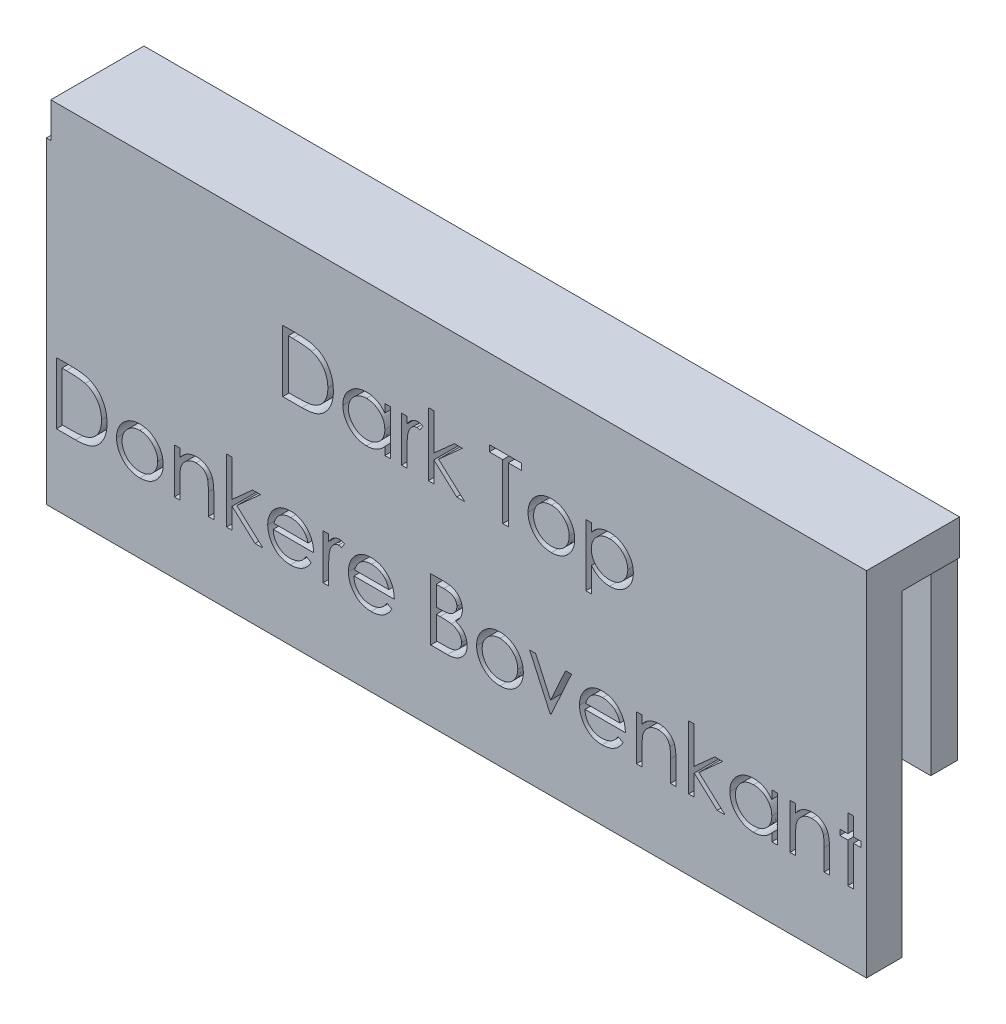
SolidWorks part; units mm, degrees
ref_plane "Front Plane" through (0, 0, 0) normal (0, 0, 1) x (1, 0, 0)
ref_plane "Top Plane" through (0, 0, 0) normal (0, 1, 0) x (1, 0, 0)
ref_plane "Right Plane" through (0, 0, 0) normal (1, 0, 0) x (0, 0, -1)
sketch "Sketch1" plane through (0, 0, 0) normal (0, 0, 1) x (1, 0, 0)
  line L0 (61.5, 25) -> (3, 25) construction
  line L1 (9, 25) -> (55.5, 25)
  line L2 (9, 25) -> (9, 7)
  line L3 (9, 7) -> (55.5, 7)
  line L4 (55.5, 25) -> (55.5, 7)
  line L5 (55.5, 15) -> (55.5, 25) construction
  line L6 (9, 15) -> (9, 25) construction
  line L7 (2, 2) -> (62.5, 2) construction
  dimension "D1" = 5
extrude "Boss-Extrude1" add sketch "Sketch1" along normal blind 2
sketch "Sketch3" plane through (0, 15, 0) normal (0, 1, 0) x (1, 0, 0)
  line L0 (9.2511, 3.2803) -> (9.2511, 1.7537)
  line L5 (9.2511, 1.7537) -> (55.39, 1.7537)
  line L6 (55.39, 3.2803) -> (55.39, 1.7537)
  line L7 (9.2511, 3.2803) -> (55.39, 3.2803)
extrude "Boss-Extrude2" add sketch "Sketch3" along normal up to surface (10 mm away) separate body
sketch "Sketch4" plane through (0, 25, 0) normal (0, 1, 0) x (1, 0, 0)
  line L1 (9.2511, 3.2803) -> (55.5, 3.2803)
  line L2 (9.2511, 3.2803) -> (9.2511, -2)
  line L3 (9.2511, -2) -> (55.5, -2)
  line L4 (55.5, 3.2803) -> (55.5, -2)
extrude "Boss-Extrude3" add sketch "Sketch4" along normal blind 2
sketch "Sketch5" plane through (0, 0, 2) normal (0, 0, 1) x (1, 0, 0)
  line L0 (9, 19) -> (55.5, 19) construction
  line L1 (9, 25) -> (9, 7) construction
  line L2 (55.5, 7) -> (55.5, 27) construction
  line L3 (9.2511, 27) -> (55.5, 27) construction
  line L4 (9, 11) -> (55.5, 11) construction
  line L161 (22.4006, 19) -> (22.4006, 22.5)
  line L162 (22.4006, 22.5) -> (23.1074, 22.5)
  line L163 (23.4853, 19) -> (22.4006, 19)
  line L164 (22.7147, 19.359) -> (23.1165, 19.359)
  line L165 (22.9608, 22.141) -> (22.7147, 22.141)
  line L166 (22.7147, 22.141) -> (22.7147, 19.359)
  line L167 (28.5032, 21.5577) -> (28.5032, 19)
  line L168 (28.5032, 19) -> (28.1891, 19)
  line L169 (28.1891, 19) -> (28.1891, 19.4424)
  line L170 (28.1891, 21.0844) -> (28.1891, 21.5577)
  line L171 (28.1891, 21.5577) -> (28.5032, 21.5577)
  line L172 (29.1314, 21.5577) -> (29.4455, 21.5577)
  line L173 (29.4455, 21.5577) -> (29.4455, 21.1812)
  line L174 (30.3429, 21.5149) -> (30.1705, 21.2429)
  line L175 (29.4455, 19.8596) -> (29.4455, 19)
  line L176 (29.4455, 19) -> (29.1314, 19)
  line L177 (29.1314, 19) -> (29.1314, 21.5577)
  line L178 (30.6571, 22.5897) -> (30.9712, 22.5897)
  line L179 (30.9712, 22.5897) -> (30.9712, 20.5144)
  line L180 (30.9712, 20.5144) -> (32.135, 21.5577)
  line L181 (32.135, 21.5577) -> (32.5865, 21.5577)
  line L182 (32.5865, 21.5577) -> (31.2362, 20.3462)
  line L183 (31.2362, 20.3462) -> (32.7212, 19)
  line L184 (32.7212, 19) -> (32.2703, 19)
  line L185 (32.2703, 19) -> (30.9712, 20.1786)
  line L186 (30.9712, 20.1786) -> (30.9712, 19)
  line L187 (30.9712, 19) -> (30.6571, 19)
  line L188 (30.6571, 19) -> (30.6571, 22.5897)
  line L189 (34.1122, 22.141) -> (34.1122, 22.5)
  line L190 (34.1122, 22.5) -> (35.9519, 22.5)
  line L191 (35.9519, 22.5) -> (35.9519, 22.141)
  line L192 (35.9519, 22.141) -> (35.1891, 22.141)
  line L193 (35.1891, 22.141) -> (35.1891, 19)
  line L194 (35.1891, 19) -> (34.875, 19)
  line L195 (34.875, 19) -> (34.875, 22.141)
  line L196 (34.875, 22.141) -> (34.1122, 22.141)
  line L197 (39.5865, 21.5577) -> (39.9006, 21.5577)
  line L198 (39.9006, 21.5577) -> (39.9006, 21.0844)
  line L199 (39.9006, 19.4634) -> (39.9006, 18.0577)
  line L200 (39.9006, 18.0577) -> (39.5865, 18.0577)
  line L201 (39.5865, 18.0577) -> (39.5865, 21.5577)
  line L202 (9.5673, 11) -> (9.5673, 14.5)
  line L203 (9.5673, 14.5) -> (10.274, 14.5)
  line L204 (10.6519, 11) -> (9.5673, 11)
  line L205 (9.8814, 11.359) -> (10.2832, 11.359)
  line L206 (10.1275, 14.141) -> (9.8814, 14.141)
  line L207 (9.8814, 14.141) -> (9.8814, 11.359)
  line L208 (16.2532, 13.5577) -> (16.5673, 13.5577)
  line L209 (16.5673, 13.5577) -> (16.5673, 13.0964)
  line L210 (18.4968, 12.3062) -> (18.4968, 11)
  line L211 (18.4968, 11) -> (18.1827, 11)
  line L212 (18.1827, 11) -> (18.1827, 12.2031)
  line L213 (16.5673, 11.9248) -> (16.5673, 11)
  line L214 (16.5673, 11) -> (16.2532, 11)
  line L215 (16.2532, 11) -> (16.2532, 13.5577)
  line L216 (19.2147, 14.5897) -> (19.5288, 14.5897)
  line L217 (19.5288, 14.5897) -> (19.5288, 12.5144)
  line L218 (19.5288, 12.5144) -> (20.6927, 13.5577)
  line L219 (20.6927, 13.5577) -> (21.1442, 13.5577)
  line L220 (21.1442, 13.5577) -> (19.7939, 12.3462)
  line L221 (19.7939, 12.3462) -> (21.2788, 11)
  line L222 (21.2788, 11) -> (20.828, 11)
  line L223 (20.828, 11) -> (19.5288, 12.1786)
  line L224 (19.5288, 12.1786) -> (19.5288, 11)
  line L225 (19.5288, 11) -> (19.2147, 11)
  line L226 (19.2147, 11) -> (19.2147, 14.5897)
  line L227 (23.737, 11.8077) -> (24.016, 11.6612)
  line L228 (24.1506, 12.2115) -> (21.8622, 12.2115)
  line L229 (21.8951, 12.5256) -> (23.8365, 12.5256)
  line L230 (24.6891, 13.5577) -> (25.0032, 13.5577)
  line L231 (25.0032, 13.5577) -> (25.0032, 13.1812)
  line L232 (25.9006, 13.5149) -> (25.7282, 13.2429)
  line L233 (25.0032, 11.8596) -> (25.0032, 11)
  line L234 (25.0032, 11) -> (24.6891, 11)
  line L235 (24.6891, 11) -> (24.6891, 13.5577)
  line L236 (28.3139, 11.8077) -> (28.5929, 11.6612)
  line L237 (28.7276, 12.2115) -> (26.4391, 12.2115)
  line L238 (26.4721, 12.5256) -> (28.4135, 12.5256)
  line L239 (30.7917, 14.5) -> (31.4746, 14.5)
  line L240 (31.7382, 11) -> (30.7917, 11)
  line L241 (30.7917, 11) -> (30.7917, 14.5)
  line L242 (31.1058, 14.141) -> (31.1058, 13.0192)
  line L243 (31.1058, 13.0192) -> (31.3168, 13.0192)
  line L244 (31.5321, 14.141) -> (31.1058, 14.141)
  line L245 (31.1058, 12.6603) -> (31.1058, 11.359)
  line L246 (31.1058, 11.359) -> (31.5531, 11.359)
  line L247 (31.314, 12.6603) -> (31.1058, 12.6603)
  line L248 (36.4006, 13.5577) -> (36.7407, 13.5577)
  line L249 (36.7407, 13.5577) -> (37.5897, 11.6955)
  line L250 (37.5897, 11.6955) -> (38.4388, 13.5577)
  line L251 (38.4388, 13.5577) -> (38.7788, 13.5577)
  line L252 (38.7788, 13.5577) -> (37.6122, 11)
  line L253 (37.6122, 11) -> (37.5673, 11)
  line L254 (37.5673, 11) -> (36.4006, 13.5577)
  line L255 (41.4165, 11.8077) -> (41.6955, 11.6612)
  line L256 (41.8301, 12.2115) -> (39.5417, 12.2115)
  line L257 (39.5746, 12.5256) -> (41.516, 12.5256)
  line L258 (42.4583, 13.5577) -> (42.7724, 13.5577)
  line L259 (42.7724, 13.5577) -> (42.7724, 13.0964)
  line L260 (44.7019, 12.3062) -> (44.7019, 11)
  line L261 (44.7019, 11) -> (44.3878, 11)
  line L262 (44.3878, 11) -> (44.3878, 12.2031)
  line L263 (42.7724, 11.9248) -> (42.7724, 11)
  line L264 (42.7724, 11) -> (42.4583, 11)
  line L265 (42.4583, 11) -> (42.4583, 13.5577)
  line L266 (45.4199, 14.5897) -> (45.734, 14.5897)
  line L267 (45.734, 14.5897) -> (45.734, 12.5144)
  line L268 (45.734, 12.5144) -> (46.8978, 13.5577)
  line L269 (46.8978, 13.5577) -> (47.3494, 13.5577)
  line L270 (47.3494, 13.5577) -> (45.999, 12.3462)
  line L271 (45.999, 12.3462) -> (47.484, 11)
  line L272 (47.484, 11) -> (47.0332, 11)
  line L273 (47.0332, 11) -> (45.734, 12.1786)
  line L274 (45.734, 12.1786) -> (45.734, 11)
  line L275 (45.734, 11) -> (45.4199, 11)
  line L276 (45.4199, 11) -> (45.4199, 14.5897)
  line L277 (50.4455, 13.5577) -> (50.4455, 11)
  line L278 (50.4455, 11) -> (50.1314, 11)
  line L279 (50.1314, 11) -> (50.1314, 11.4424)
  line L280 (50.1314, 13.0844) -> (50.1314, 13.5577)
  line L281 (50.1314, 13.5577) -> (50.4455, 13.5577)
  line L282 (51.1635, 13.5577) -> (51.4776, 13.5577)
  line L283 (51.4776, 13.5577) -> (51.4776, 13.0964)
  line L284 (53.4071, 12.3062) -> (53.4071, 11)
  line L285 (53.4071, 11) -> (53.0929, 11)
  line L286 (53.0929, 11) -> (53.0929, 12.2031)
  line L287 (51.4776, 11.9248) -> (51.4776, 11)
  line L288 (51.4776, 11) -> (51.1635, 11)
  line L289 (51.1635, 11) -> (51.1635, 13.5577)
  line L290 (54.4391, 14.5897) -> (54.7532, 14.5897)
  line L291 (54.7532, 14.5897) -> (54.7532, 13.5577)
  line L292 (54.7532, 13.5577) -> (55.2019, 13.5577)
  line L293 (55.2019, 13.5577) -> (55.2019, 13.2436)
  line L294 (55.2019, 13.2436) -> (54.7532, 13.2436)
  line L295 (54.7532, 13.2436) -> (54.7532, 11)
  line L296 (54.7532, 11) -> (54.4391, 11)
  line L297 (54.4391, 11) -> (54.4391, 13.2436)
  line L298 (54.4391, 13.2436) -> (53.9904, 13.2436)
  line L299 (53.9904, 13.2436) -> (53.9904, 13.5577)
  line L300 (53.9904, 13.5577) -> (54.4391, 13.5577)
  line L301 (54.4391, 13.5577) -> (54.4391, 14.5897)
  spline S0 degree 3 poles (23.1074, 22.5) (23.2261, 22.4995) (23.3978, 22.497) (23.618, 22.4837) (23.7634, 22.4697) (23.8959, 22.4525) (24.0472, 22.4254) (24.1529, 22.3968) (24.2179, 22.3738) knots 0 0 0 0 0.317406 0.458844 0.589367 0.707831 0.81577 1 1 1 1
  spline S1 degree 3 poles (24.2179, 22.3738) (24.2987, 22.3452) (24.4155, 22.293) (24.5598, 22.2051) (24.6611, 22.1321) (24.7539, 22.0494) (24.8419, 21.9603) (24.9215, 21.8617) (24.9944, 21.7556) (25.0601, 21.6433) (25.1173, 21.525) (25.1647, 21.4012) (25.2041, 21.2724) (25.2351, 21.1382) (25.264, 20.9492) (25.273, 20.804) (25.2724, 20.7058) knots 0 0 0 0 0.121694 0.181155 0.239875 0.298702 0.357647 0.417605 0.478494 0.540407 0.602345 0.665004 0.728559 0.793651 0.860534 1 1 1 1
  spline S2 degree 3 poles (25.2724, 20.7058) (25.2728, 20.6205) (25.2653, 20.4946) (25.2432, 20.3298) (25.2182, 20.2122) (25.1878, 20.0978) (25.1489, 19.988) (25.1042, 19.8817) (25.0522, 19.7802) (24.995, 19.6842) (24.9337, 19.5936) (24.8683, 19.5098) (24.7981, 19.4326) (24.7241, 19.362) (24.6458, 19.2975) (24.5629, 19.2404) (24.4759, 19.1883) (24.3822, 19.1429) (24.2801, 19.1044) (24.1691, 19.0726) (24.0494, 19.046) (23.9209, 19.025) (23.7321, 19.0054) (23.5857, 18.9995) (23.4853, 19) knots 0 0 0 0 0.090807 0.134295 0.177024 0.218823 0.260244 0.30108 0.341614 0.381583 0.42012 0.458075 0.494738 0.531195 0.566934 0.602713 0.638327 0.674853 0.713467 0.754442 0.797815 0.843989 0.893072 1 1 1 1
  spline S3 degree 3 poles (23.1165, 19.359) (23.2275, 19.359) (23.3872, 19.3611) (23.5908, 19.3707) (23.7229, 19.3803) (23.8412, 19.393) (23.9721, 19.4105) (24.0624, 19.4308) (24.117, 19.448) knots 0 0 0 0 0.330628 0.475549 0.606746 0.725024 0.829742 1 1 1 1
  spline S4 degree 3 poles (24.117, 19.448) (24.1803, 19.4695) (24.2735, 19.5053) (24.3877, 19.5701) (24.4678, 19.6235) (24.5421, 19.6842) (24.6116, 19.7507) (24.6759, 19.8236) (24.7346, 19.9026) (24.7871, 19.9873) (24.8326, 20.0768) (24.8725, 20.1702) (24.9037, 20.2689) (24.9282, 20.372) (24.9519, 20.5179) (24.9584, 20.6304) (24.9583, 20.7065) knots 0 0 0 0 0.123338 0.183125 0.241783 0.300579 0.35968 0.418882 0.479531 0.540851 0.602303 0.664463 0.727806 0.792895 0.859672 1 1 1 1
  spline S5 degree 3 poles (24.9583, 20.7065) (24.9593, 20.787) (24.9509, 20.9055) (24.9256, 21.0593) (24.8988, 21.1683) (24.8647, 21.273) (24.8221, 21.3728) (24.7734, 21.4688) (24.7155, 21.5588) (24.6521, 21.6439) (24.5817, 21.7219) (24.5055, 21.7929) (24.4243, 21.858) (24.3357, 21.9146) (24.2092, 21.9832) (24.1064, 22.0211) (24.0364, 22.0429) knots 0 0 0 0 0.137813 0.203226 0.267174 0.330024 0.391794 0.453084 0.514334 0.575 0.634865 0.694116 0.753442 0.813126 0.87408 1 1 1 1
  spline S6 degree 3 poles (24.0364, 22.0429) (23.9743, 22.0616) (23.8729, 22.0829) (23.7281, 22.1036) (23.6002, 22.1177) (23.4592, 22.1278) (23.2447, 22.1384) (23.077, 22.1414) (22.9608, 22.141) knots 0 0 0 0 0.179285 0.286583 0.405111 0.535593 0.67819 1 1 1 1
  spline S7 degree 3 poles (28.1891, 19.4424) (28.1219, 19.363) (28.0134, 19.2524) (27.8467, 19.1378) (27.7181, 19.0696) (27.5831, 19.0185) (27.3931, 18.9691) (27.2447, 18.9543) (27.1444, 18.9551) knots 0 0 0 0 0.262085 0.38627 0.507165 0.6273 0.748145 1 1 1 1
  spline S8 degree 3 poles (27.1444, 18.9551) (27.0554, 18.9553) (26.9231, 18.9668) (26.7531, 19.0077) (26.6318, 19.0496) (26.5161, 19.1052) (26.4051, 19.1717) (26.2992, 19.2509) (26.2001, 19.3415) (26.1089, 19.4399) (26.0288, 19.5449) (25.9621, 19.6559) (25.9062, 19.7716) (25.8633, 19.8929) (25.8226, 20.0637) (25.8111, 20.1964) (25.8109, 20.2859) knots 0 0 0 0 0.127433 0.189004 0.24993 0.310668 0.372329 0.434939 0.499576 0.564191 0.626735 0.688109 0.749294 0.810331 0.871901 1 1 1 1
  spline S9 degree 3 poles (25.8109, 20.2859) (25.8114, 20.3737) (25.8221, 20.5043) (25.8641, 20.672) (25.9077, 20.7914) (25.9635, 20.9057) (26.0314, 21.0151) (26.1114, 21.1199) (26.2037, 21.2176) (26.3036, 21.3078) (26.4105, 21.3862) (26.5218, 21.4539) (26.639, 21.5076) (26.7606, 21.5509) (26.9318, 21.5916) (27.0648, 21.6018) (27.1542, 21.6026) knots 0 0 0 0 0.126079 0.186904 0.247574 0.308003 0.369132 0.432033 0.496791 0.561611 0.624914 0.686726 0.748079 0.809582 0.871631 1 1 1 1
  spline S10 degree 3 poles (27.1542, 21.6026) (27.2564, 21.6023) (27.4082, 21.5891) (27.6002, 21.5352) (27.7348, 21.4813) (27.862, 21.4096) (28.0239, 21.2865) (28.1272, 21.1694) (28.1891, 21.0844) knots 0 0 0 0 0.254654 0.376015 0.495255 0.614798 0.738106 1 1 1 1
  spline S11 degree 3 poles (27.1585, 21.2885) (27.068, 21.2881) (26.9326, 21.273) (26.7616, 21.2165) (26.6406, 21.1593) (26.5279, 21.0872) (26.4272, 21.0001) (26.3377, 20.9003) (26.2624, 20.7882) (26.2011, 20.668) (26.1432, 20.5009) (26.1238, 20.3698) (26.125, 20.2824) knots 0 0 0 0 0.169593 0.252476 0.336244 0.419505 0.502036 0.584775 0.669846 0.754185 0.836658 1 1 1 1
  spline S12 degree 3 poles (26.125, 20.2824) (26.1257, 20.1954) (26.1424, 20.0639) (26.2023, 19.8971) (26.2634, 19.7759) (26.3402, 19.6633) (26.429, 19.5615) (26.531, 19.474) (26.6439, 19.4008) (26.7645, 19.3417) (26.934, 19.2863) (27.0667, 19.2688) (27.1556, 19.2692) knots 0 0 0 0 0.162859 0.245484 0.330807 0.416493 0.499893 0.583048 0.667158 0.751312 0.833785 1 1 1 1
  spline S13 degree 3 poles (27.1556, 19.2692) (27.246, 19.2696) (27.3816, 19.2852) (27.5544, 19.3413) (27.6782, 19.3991) (27.7935, 19.4709) (27.897, 19.5549) (27.9845, 19.6526) (28.0587, 19.76) (28.1169, 19.8777) (28.1744, 20.0471) (28.1886, 20.1826) (28.1891, 20.2732) knots 0 0 0 0 0.168664 0.252552 0.33824 0.423103 0.505556 0.586176 0.667136 0.748499 0.830452 1 1 1 1
  spline S14 degree 3 poles (28.1891, 20.2732) (28.1889, 20.3428) (28.1801, 20.4458) (28.1488, 20.578) (28.1165, 20.6714) (28.074, 20.7601) (28.0228, 20.8445) (27.9619, 20.9244) (27.8923, 20.9985) (27.8161, 21.0662) (27.7355, 21.1265) (27.6496, 21.1761) (27.5596, 21.2172) (27.4656, 21.2498) (27.332, 21.2795) (27.2286, 21.2895) (27.1585, 21.2885) knots 0 0 0 0 0.129188 0.191219 0.251913 0.312507 0.373494 0.435152 0.498741 0.562095 0.624187 0.685476 0.746097 0.807612 0.869967 1 1 1 1
  spline S15 degree 3 poles (29.4455, 21.1812) (29.4885, 21.2489) (29.5565, 21.3427) (29.6623, 21.4454) (29.7399, 21.5039) (29.8203, 21.5477) (29.9279, 21.5903) (30.0134, 21.6022) (30.0695, 21.6026) knots 0 0 0 0 0.306112 0.438367 0.560541 0.675317 0.786114 1 1 1 1
  spline S16 degree 3 poles (30.0695, 21.6026) (30.1145, 21.6022) (30.211, 21.5853) (30.2986, 21.5418) (30.3429, 21.5149) knots 0 0 0 0 0.463523 1 1 1 1
  spline S17 degree 3 poles (30.1705, 21.2429) (30.1419, 21.2556) (30.0904, 21.2788) (30.0346, 21.2881) (30.0099, 21.2885) knots 0 0 0 0 0.56023 1 1 1 1
  spline S18 degree 3 poles (30.0099, 21.2885) (29.9584, 21.2885) (29.8795, 21.2697) (29.7846, 21.2128) (29.7264, 21.1646) (29.6814, 21.1181) (29.6492, 21.0774) (29.6197, 21.0318) (29.5916, 20.9821) (29.5659, 20.9274) (29.533, 20.8463) (29.5135, 20.7819) (29.5016, 20.7374) knots 0 0 0 0 0.191338 0.295191 0.410312 0.47193 0.536425 0.603119 0.674118 0.749332 0.828283 1 1 1 1
  spline S19 degree 3 poles (29.5016, 20.7374) (29.4899, 20.6927) (29.4784, 20.6175) (29.4662, 20.5078) (29.459, 20.4049) (29.4525, 20.2883) (29.4472, 20.105) (29.445, 19.9606) (29.4455, 19.8596) knots 0 0 0 0 0.156938 0.2586 0.375891 0.508166 0.656238 1 1 1 1
  spline S20 degree 3 poles (37.636, 21.6026) (37.7301, 21.6035) (37.8693, 21.59) (38.0475, 21.5453) (38.1733, 21.5001) (38.2916, 21.4394) (38.444, 21.3418) (38.5456, 21.2491) (38.6078, 21.1812) knots 0 0 0 0 0.258332 0.382134 0.503804 0.624693 0.746871 1 1 1 1
  spline S21 degree 3 poles (38.6078, 21.1812) (38.6648, 21.1189) (38.7412, 21.0189) (38.8234, 20.8746) (38.8725, 20.7623) (38.9112, 20.646) (38.9484, 20.483) (38.9579, 20.3568) (38.9583, 20.2718) knots 0 0 0 0 0.253834 0.376506 0.498534 0.621368 0.744565 1 1 1 1
  spline S22 degree 3 poles (38.9583, 20.2718) (38.9588, 20.1863) (38.9471, 20.0591) (38.9085, 19.8948) (38.8677, 19.7769) (38.8153, 19.663) (38.7515, 19.5536) (38.6756, 19.4485) (38.5896, 19.3485) (38.4945, 19.2563) (38.3914, 19.176) (38.2823, 19.1071) (38.1656, 19.0517) (38.0426, 19.008) (37.8665, 18.9662) (37.729, 18.9555) (37.636, 18.9551) knots 0 0 0 0 0.123337 0.183265 0.243172 0.302898 0.363774 0.425605 0.489659 0.553785 0.616222 0.677854 0.739517 0.802097 0.865866 1 1 1 1
  spline S23 degree 3 poles (37.636, 18.9551) (37.5426, 18.9556) (37.4046, 18.966) (37.2281, 19.008) (37.1048, 19.0518) (36.9877, 19.1071) (36.8779, 19.1757) (36.7747, 19.2563) (36.6796, 19.3484) (36.5936, 19.4485) (36.5178, 19.5536) (36.4539, 19.663) (36.4015, 19.7769) (36.3607, 19.8948) (36.3221, 20.0591) (36.3104, 20.1863) (36.3109, 20.2718) knots 0 0 0 0 0.134635 0.198324 0.260825 0.322714 0.384555 0.446913 0.510958 0.574931 0.636685 0.697483 0.757134 0.816966 0.876818 1 1 1 1
  spline S24 degree 3 poles (36.3109, 20.2718) (36.3114, 20.3565) (36.3209, 20.4825) (36.358, 20.645) (36.3966, 20.761) (36.4462, 20.8727) (36.5273, 21.0175) (36.605, 21.1166) (36.6615, 21.1791) knots 0 0 0 0 0.255238 0.378679 0.501088 0.622714 0.746241 1 1 1 1
  spline S25 degree 3 poles (36.6615, 21.1791) (36.7231, 21.2479) (36.8256, 21.3398) (36.9776, 21.4393) (37.0973, 21.4988) (37.223, 21.5456) (37.4018, 21.5899) (37.5415, 21.6034) (37.636, 21.6026) knots 0 0 0 0 0.252713 0.374819 0.496436 0.617911 0.741288 1 1 1 1
  spline S26 degree 3 poles (37.6346, 21.2885) (37.5676, 21.2883) (37.4681, 21.2792) (37.3401, 21.2481) (37.2487, 21.2156) (37.161, 21.1735) (37.0771, 21.1218) (36.9967, 21.0611) (36.9213, 20.9917) (36.8521, 20.9158) (36.7917, 20.8349) (36.7402, 20.7504) (36.6974, 20.6622) (36.6655, 20.5693) (36.6341, 20.4391) (36.6252, 20.3379) (36.625, 20.2697) knots 0 0 0 0 0.126044 0.187165 0.247399 0.30838 0.36978 0.432584 0.497641 0.562401 0.625557 0.687332 0.748313 0.809791 0.871768 1 1 1 1
  spline S27 degree 3 poles (36.625, 20.2697) (36.6252, 20.181) (36.6408, 20.0477) (36.6992, 19.8798) (36.7577, 19.7601) (36.8311, 19.6495) (36.9176, 19.5508) (37.0162, 19.4656) (37.1259, 19.3949) (37.2442, 19.3388) (37.4126, 19.285) (37.5453, 19.2682) (37.6346, 19.2692) knots 0 0 0 0 0.168179 0.251488 0.335841 0.419834 0.502345 0.583649 0.665931 0.748717 0.831047 1 1 1 1
  spline S28 degree 3 poles (37.6346, 19.2692) (37.7239, 19.2683) (37.8565, 19.2847) (38.0245, 19.339) (38.1427, 19.3949) (38.2523, 19.4659) (38.3516, 19.5503) (38.4374, 19.6497) (38.5107, 19.7603) (38.5702, 19.8796) (38.6283, 20.0478) (38.6441, 20.181) (38.6442, 20.2697) knots 0 0 0 0 0.168983 0.250908 0.333708 0.416005 0.49766 0.579893 0.663902 0.748466 0.831791 1 1 1 1
  spline S29 degree 3 poles (38.6442, 20.2697) (38.644, 20.3379) (38.6351, 20.4391) (38.6037, 20.5693) (38.5718, 20.6621) (38.5291, 20.7506) (38.4767, 20.8347) (38.4165, 20.9161) (38.3465, 20.9914) (38.2712, 21.0611) (38.1907, 21.1218) (38.1069, 21.1732) (38.0195, 21.2159) (37.9281, 21.2478) (37.8005, 21.2795) (37.7013, 21.2881) (37.6346, 21.2885) knots 0 0 0 0 0.128274 0.19027 0.251768 0.312769 0.374793 0.43797 0.503047 0.568125 0.63095 0.692369 0.752973 0.813641 0.874355 1 1 1 1
  spline S30 degree 3 poles (39.9006, 21.0844) (39.9628, 21.1697) (40.0672, 21.2857) (40.2285, 21.4098) (40.3556, 21.4813) (40.4901, 21.535) (40.6813, 21.5892) (40.8324, 21.6022) (40.9341, 21.6026) knots 0 0 0 0 0.263045 0.386061 0.505771 0.625178 0.746148 1 1 1 1
  spline S31 degree 3 poles (40.9341, 21.6026) (41.0237, 21.6017) (41.157, 21.5917) (41.3284, 21.5509) (41.45, 21.5076) (41.5673, 21.4539) (41.6785, 21.3862) (41.7854, 21.3078) (41.8853, 21.2176) (41.9776, 21.1199) (42.0575, 21.0149) (42.1264, 20.9059) (42.182, 20.7913) (42.2256, 20.672) (42.2676, 20.5043) (42.2783, 20.3737) (42.2788, 20.2859) knots 0 0 0 0 0.128636 0.190653 0.252125 0.313446 0.375227 0.438498 0.503285 0.56801 0.630879 0.692154 0.752552 0.813191 0.873985 1 1 1 1
  spline S32 degree 3 poles (42.2788, 20.2859) (42.2786, 20.1963) (42.2671, 20.0637) (42.2265, 19.8929) (42.1835, 19.7717) (42.1278, 19.6557) (42.0601, 19.5451) (41.9802, 19.4399) (41.8889, 19.3415) (41.7899, 19.2509) (41.684, 19.1717) (41.5729, 19.1052) (41.4572, 19.0496) (41.336, 19.0077) (41.1657, 18.9668) (41.0332, 18.9555) (40.9439, 18.9551) knots 0 0 0 0 0.128034 0.189574 0.25058 0.311733 0.37325 0.435763 0.500346 0.564949 0.627528 0.689157 0.749865 0.81076 0.8723 1 1 1 1
  spline S33 degree 3 poles (40.9439, 18.9551) (40.8434, 18.954) (40.6949, 18.9711) (40.5046, 19.0237) (40.3704, 19.0803) (40.2423, 19.1526) (40.0772, 19.2721) (39.9682, 19.3833) (39.9006, 19.4634) knots 0 0 0 0 0.250548 0.37123 0.492116 0.613401 0.737997 1 1 1 1
  spline S34 degree 3 poles (40.9313, 21.2885) (40.8612, 21.2895) (40.7578, 21.2794) (40.6241, 21.2498) (40.53, 21.2169) (40.4397, 21.1765) (40.354, 21.1261) (40.273, 21.0664) (40.1968, 20.9987) (40.1279, 20.9242) (40.0669, 20.8446) (40.0157, 20.7601) (39.9732, 20.6714) (39.9409, 20.578) (39.9097, 20.4458) (39.9008, 20.3428) (39.9006, 20.2732) knots 0 0 0 0 0.130024 0.192374 0.253884 0.314896 0.375806 0.438242 0.501591 0.564881 0.626533 0.687516 0.748106 0.808796 0.870822 1 1 1 1
  spline S35 degree 3 poles (39.9006, 20.2732) (39.9008, 20.1825) (39.9159, 20.0474) (39.972, 19.8775) (40.0304, 19.7601) (40.1044, 19.6521) (40.1935, 19.5554) (40.2969, 19.4706) (40.413, 19.3992) (40.5374, 19.3413) (40.7106, 19.2855) (40.8461, 19.2694) (40.9362, 19.2692) knots 0 0 0 0 0.169344 0.251061 0.332326 0.413189 0.494299 0.576654 0.661785 0.747765 0.831967 1 1 1 1
  spline S36 degree 3 poles (40.9362, 19.2692) (41.0247, 19.2687) (41.1569, 19.2866) (41.3258, 19.3415) (41.446, 19.401) (41.5588, 19.474) (41.6607, 19.5616) (41.7497, 19.6631) (41.8255, 19.7761) (41.8866, 19.8972) (41.9479, 20.0637) (41.9637, 20.1955) (41.9647, 20.2824) knots 0 0 0 0 0.165574 0.248159 0.332033 0.416257 0.499525 0.583039 0.668596 0.754035 0.83692 1 1 1 1
  spline S37 degree 3 poles (41.9647, 20.2824) (41.966, 20.3699) (41.9464, 20.5008) (41.8889, 20.6682) (41.8264, 20.7877) (41.7522, 20.9005) (41.6624, 21.0001) (41.5618, 21.0872) (41.4491, 21.1593) (41.3282, 21.2165) (41.1572, 21.273) (41.0218, 21.2881) (40.9313, 21.2885) knots 0 0 0 0 0.163349 0.245826 0.330367 0.415198 0.497941 0.580476 0.66374 0.747513 0.830399 1 1 1 1
  spline S38 degree 3 poles (10.274, 14.5) (10.3928, 14.4995) (10.5645, 14.497) (10.7847, 14.4837) (10.9301, 14.4697) (11.0626, 14.4525) (11.2139, 14.4254) (11.3196, 14.3968) (11.3846, 14.3738) knots 0 0 0 0 0.317406 0.458844 0.589367 0.707831 0.81577 1 1 1 1
  spline S39 degree 3 poles (11.3846, 14.3738) (11.4653, 14.3452) (11.5822, 14.293) (11.7265, 14.2051) (11.8277, 14.1321) (11.9205, 14.0494) (12.0085, 13.9603) (12.0882, 13.8617) (12.1611, 13.7556) (12.2268, 13.6433) (12.2839, 13.525) (12.3314, 13.4012) (12.3708, 13.2724) (12.4018, 13.1382) (12.4306, 12.9492) (12.4396, 12.804) (12.4391, 12.7058) knots 0 0 0 0 0.121694 0.181155 0.239875 0.298702 0.357647 0.417605 0.478494 0.540407 0.602345 0.665004 0.728559 0.793651 0.860534 1 1 1 1
  spline S40 degree 3 poles (12.4391, 12.7058) (12.4395, 12.6205) (12.4319, 12.4946) (12.4099, 12.3298) (12.3849, 12.2122) (12.3545, 12.0978) (12.3155, 11.988) (12.2709, 11.8817) (12.2188, 11.7802) (12.1617, 11.6842) (12.1004, 11.5936) (12.0349, 11.5098) (11.9648, 11.4326) (11.8907, 11.362) (11.8124, 11.2975) (11.7296, 11.2404) (11.6426, 11.1883) (11.5489, 11.1429) (11.4468, 11.1044) (11.3357, 11.0726) (11.2161, 11.046) (11.0876, 11.025) (10.8988, 11.0054) (10.7523, 10.9995) (10.6519, 11) knots 0 0 0 0 0.090807 0.134295 0.177024 0.218823 0.260244 0.30108 0.341614 0.381583 0.42012 0.458075 0.494738 0.531195 0.566934 0.602713 0.638327 0.674853 0.713467 0.754442 0.797815 0.843989 0.893072 1 1 1 1
  spline S41 degree 3 poles (10.2832, 11.359) (10.3942, 11.359) (10.5539, 11.3611) (10.7575, 11.3707) (10.8896, 11.3803) (11.0079, 11.393) (11.1388, 11.4105) (11.2291, 11.4308) (11.2837, 11.448) knots 0 0 0 0 0.330628 0.475549 0.606746 0.725024 0.829742 1 1 1 1
  spline S42 degree 3 poles (11.2837, 11.448) (11.3469, 11.4695) (11.4401, 11.5053) (11.5544, 11.5701) (11.6345, 11.6235) (11.7088, 11.6842) (11.7782, 11.7507) (11.8426, 11.8236) (11.9013, 11.9026) (11.9538, 11.9873) (11.9993, 12.0768) (12.0391, 12.1702) (12.0704, 12.2689) (12.0949, 12.372) (12.1186, 12.5179) (12.125, 12.6304) (12.125, 12.7065) knots 0 0 0 0 0.123338 0.183125 0.241783 0.300579 0.35968 0.418882 0.479531 0.540851 0.602303 0.664463 0.727806 0.792895 0.859672 1 1 1 1
  spline S43 degree 3 poles (12.125, 12.7065) (12.1259, 12.787) (12.1176, 12.9055) (12.0923, 13.0593) (12.0655, 13.1683) (12.0314, 13.273) (11.9888, 13.3728) (11.9401, 13.4688) (11.8822, 13.5588) (11.8188, 13.6439) (11.7484, 13.7219) (11.6722, 13.7929) (11.591, 13.858) (11.5024, 13.9146) (11.3758, 13.9832) (11.2731, 14.0211) (11.203, 14.0429) knots 0 0 0 0 0.137813 0.203226 0.267174 0.330024 0.391794 0.453084 0.514334 0.575 0.634865 0.694116 0.753442 0.813126 0.87408 1 1 1 1
  spline S44 degree 3 poles (11.203, 14.0429) (11.141, 14.0616) (11.0396, 14.0829) (10.8948, 14.1036) (10.7669, 14.1177) (10.6259, 14.1278) (10.4114, 14.1384) (10.2437, 14.1414) (10.1275, 14.141) knots 0 0 0 0 0.179285 0.286583 0.405111 0.535593 0.67819 1 1 1 1
  spline S45 degree 3 poles (14.3027, 13.6026) (14.3968, 13.6035) (14.536, 13.59) (14.7141, 13.5453) (14.8399, 13.5001) (14.9583, 13.4394) (15.1107, 13.3418) (15.2123, 13.2491) (15.2744, 13.1812) knots 0 0 0 0 0.258332 0.382134 0.503804 0.624693 0.746871 1 1 1 1
  spline S46 degree 3 poles (15.2744, 13.1812) (15.3315, 13.1189) (15.4079, 13.0189) (15.4901, 12.8746) (15.5392, 12.7623) (15.5778, 12.646) (15.615, 12.483) (15.6245, 12.3568) (15.625, 12.2718) knots 0 0 0 0 0.253834 0.376506 0.498534 0.621368 0.744565 1 1 1 1
  spline S47 degree 3 poles (15.625, 12.2718) (15.6255, 12.1863) (15.6138, 12.0591) (15.5752, 11.8948) (15.5344, 11.7769) (15.482, 11.663) (15.4181, 11.5536) (15.3423, 11.4485) (15.2562, 11.3485) (15.1612, 11.2563) (15.0581, 11.176) (14.9489, 11.1071) (14.8323, 11.0517) (14.7092, 11.008) (14.5332, 10.9662) (14.3956, 10.9555) (14.3027, 10.9551) knots 0 0 0 0 0.123337 0.183265 0.243172 0.302898 0.363774 0.425605 0.489659 0.553785 0.616222 0.677854 0.739517 0.802097 0.865866 1 1 1 1
  spline S48 degree 3 poles (14.3027, 10.9551) (14.2093, 10.9556) (14.0713, 10.966) (13.8947, 11.008) (13.7715, 11.0518) (13.6544, 11.1071) (13.5446, 11.1757) (13.4414, 11.2563) (13.3463, 11.3484) (13.2603, 11.4485) (13.1844, 11.5536) (13.1206, 11.663) (13.0682, 11.7769) (13.0274, 11.8948) (12.9888, 12.0591) (12.9771, 12.1863) (12.9776, 12.2718) knots 0 0 0 0 0.134635 0.198324 0.260825 0.322714 0.384555 0.446913 0.510958 0.574931 0.636685 0.697483 0.757134 0.816966 0.876818 1 1 1 1
  spline S49 degree 3 poles (12.9776, 12.2718) (12.9781, 12.3565) (12.9876, 12.4825) (13.0246, 12.645) (13.0633, 12.761) (13.1129, 12.8727) (13.194, 13.0175) (13.2717, 13.1166) (13.3281, 13.1791) knots 0 0 0 0 0.255238 0.378679 0.501088 0.622714 0.746241 1 1 1 1
  spline S50 degree 3 poles (13.3281, 13.1791) (13.3897, 13.2479) (13.4923, 13.3398) (13.6443, 13.4393) (13.7639, 13.4988) (13.8896, 13.5456) (14.0685, 13.5899) (14.2081, 13.6034) (14.3027, 13.6026) knots 0 0 0 0 0.252713 0.374819 0.496436 0.617911 0.741288 1 1 1 1
  spline S51 degree 3 poles (14.3013, 13.2885) (14.2343, 13.2883) (14.1348, 13.2792) (14.0068, 13.2481) (13.9153, 13.2156) (13.8277, 13.1735) (13.7438, 13.1218) (13.6634, 13.0611) (13.588, 12.9917) (13.5188, 12.9158) (13.4583, 12.8349) (13.4069, 12.7504) (13.3641, 12.6622) (13.3322, 12.5693) (13.3007, 12.4391) (13.2919, 12.3379) (13.2917, 12.2697) knots 0 0 0 0 0.126044 0.187165 0.247399 0.30838 0.36978 0.432584 0.497641 0.562401 0.625557 0.687332 0.748313 0.809791 0.871768 1 1 1 1
  spline S52 degree 3 poles (13.2917, 12.2697) (13.2919, 12.181) (13.3075, 12.0477) (13.3658, 11.8798) (13.4244, 11.7601) (13.4978, 11.6495) (13.5843, 11.5508) (13.6829, 11.4656) (13.7925, 11.3949) (13.9109, 11.3388) (14.0793, 11.285) (14.212, 11.2682) (14.3013, 11.2692) knots 0 0 0 0 0.168179 0.251488 0.335841 0.419834 0.502345 0.583649 0.665931 0.748717 0.831047 1 1 1 1
  spline S53 degree 3 poles (14.3013, 11.2692) (14.3905, 11.2683) (14.5231, 11.2847) (14.6912, 11.339) (14.8094, 11.3949) (14.919, 11.4659) (15.0183, 11.5503) (15.104, 11.6497) (15.1774, 11.7603) (15.2369, 11.8796) (15.2949, 12.0478) (15.3107, 12.181) (15.3109, 12.2697) knots 0 0 0 0 0.168983 0.250908 0.333708 0.416005 0.49766 0.579893 0.663902 0.748466 0.831791 1 1 1 1
  spline S54 degree 3 poles (15.3109, 12.2697) (15.3107, 12.3379) (15.3018, 12.4391) (15.2704, 12.5693) (15.2385, 12.6621) (15.1958, 12.7506) (15.1434, 12.8347) (15.0831, 12.9161) (15.0131, 12.9914) (14.9378, 13.0611) (14.8574, 13.1218) (14.7736, 13.1732) (14.6862, 13.2159) (14.5947, 13.2478) (14.4672, 13.2795) (14.368, 13.2881) (14.3013, 13.2885) knots 0 0 0 0 0.128274 0.19027 0.251768 0.312769 0.374793 0.43797 0.503047 0.568125 0.63095 0.692369 0.752973 0.813641 0.874355 1 1 1 1
  spline S55 degree 3 poles (16.5673, 13.0964) (16.6307, 13.1786) (16.7316, 13.2935) (16.8889, 13.414) (17.0089, 13.4842) (17.1345, 13.537) (17.31, 13.5886) (17.448, 13.6021) (17.5405, 13.6026) knots 0 0 0 0 0.273569 0.398988 0.51993 0.63811 0.756589 1 1 1 1
  spline S56 degree 3 poles (17.5405, 13.6026) (17.6328, 13.602) (17.7707, 13.5869) (17.9413, 13.5242) (18.0579, 13.461) (18.163, 13.3824) (18.2554, 13.2908) (18.3317, 13.1855) (18.3829, 13.0878) (18.4166, 13.0011) (18.4379, 12.9269) (18.4559, 12.8441) (18.4715, 12.7532) (18.4821, 12.6534) (18.4937, 12.5037) (18.4976, 12.3869) (18.4968, 12.3062) knots 0 0 0 0 0.151178 0.223488 0.295543 0.366976 0.437131 0.507044 0.57856 0.616614 0.658756 0.704491 0.754803 0.809332 0.868274 1 1 1 1
  spline S57 degree 3 poles (18.1827, 12.2031) (18.1822, 12.2697) (18.1821, 12.3651) (18.1782, 12.4864) (18.1742, 12.5638) (18.1684, 12.632) (18.1611, 12.705) (18.1526, 12.755) (18.1455, 12.7851) knots 0 0 0 0 0.34211 0.489826 0.623254 0.74008 0.841483 1 1 1 1
  spline S58 degree 3 poles (18.1455, 12.7851) (18.128, 12.8619) (18.0883, 12.9715) (18.0001, 13.0931) (17.9222, 13.1653) (17.831, 13.2214) (17.6866, 13.2756) (17.5674, 13.2889) (17.4858, 13.2885) knots 0 0 0 0 0.260833 0.378476 0.493178 0.609281 0.729981 1 1 1 1
  spline S59 degree 3 poles (17.4858, 13.2885) (17.4358, 13.2887) (17.3611, 13.283) (17.2644, 13.2621) (17.194, 13.2413) (17.1265, 13.2126) (17.0597, 13.1801) (16.9962, 13.1395) (16.9346, 13.0943) (16.8773, 13.0443) (16.824, 12.9914) (16.7765, 12.9351) (16.7334, 12.8763) (16.6962, 12.8142) (16.6527, 12.7275) (16.6283, 12.6584) (16.6157, 12.6112) knots 0 0 0 0 0.126627 0.188984 0.25023 0.312351 0.374574 0.438148 0.50292 0.567974 0.630771 0.692935 0.754398 0.815218 0.876117 1 1 1 1
  spline S60 degree 3 poles (16.6157, 12.6112) (16.6063, 12.5738) (16.5959, 12.5123) (16.5855, 12.4234) (16.5785, 12.3425) (16.5742, 12.2518) (16.5676, 12.1116) (16.5678, 12.0014) (16.5673, 11.9248) knots 0 0 0 0 0.167615 0.271052 0.38946 0.520843 0.666399 1 1 1 1
  spline S61 degree 3 poles (24.016, 11.6612) (23.9745, 11.5835) (23.9051, 11.4745) (23.7981, 11.3447) (23.713, 11.263) (23.6234, 11.1917) (23.5286, 11.1294) (23.4283, 11.0763) (23.3225, 11.0315) (23.2102, 10.9971) (23.0478, 10.9638) (22.9209, 10.9551) (22.8346, 10.9551) knots 0 0 0 0 0.181661 0.265874 0.346355 0.4246 0.501903 0.579992 0.658443 0.738672 0.821894 1 1 1 1
  spline S62 degree 3 poles (22.8346, 10.9551) (22.7389, 10.9552) (22.5979, 10.9662) (22.4187, 11.0093) (22.2955, 11.0532) (22.1808, 11.1107) (22.0743, 11.1806) (21.9754, 11.2628) (21.8874, 11.3578) (21.8082, 11.4595) (21.7382, 11.5654) (21.6798, 11.6754) (21.6322, 11.7887) (21.5939, 11.9045) (21.5578, 12.065) (21.549, 12.1888) (21.5481, 12.2718) knots 0 0 0 0 0.139629 0.204797 0.268135 0.329814 0.391301 0.453434 0.516552 0.579631 0.641119 0.701294 0.76081 0.819932 0.87892 1 1 1 1
  spline S63 degree 3 poles (21.5481, 12.2718) (21.549, 12.3496) (21.5563, 12.4658) (21.5879, 12.6163) (21.6201, 12.7252) (21.6617, 12.8307) (21.7298, 12.9682) (21.795, 13.0643) (21.8425, 13.1258) knots 0 0 0 0 0.253768 0.377428 0.500551 0.623296 0.746578 1 1 1 1
  spline S64 degree 3 poles (21.8425, 13.1258) (21.9031, 13.2015) (22.0019, 13.3074) (22.1566, 13.4182) (22.2781, 13.4862) (22.4085, 13.5378) (22.595, 13.5903) (22.7429, 13.6014) (22.8423, 13.6026) knots 0 0 0 0 0.253589 0.374643 0.49534 0.616325 0.739759 1 1 1 1
  spline S65 degree 3 poles (22.8423, 13.6026) (22.9452, 13.603) (23.0971, 13.5881) (23.2897, 13.5348) (23.4235, 13.4797) (23.5492, 13.4085) (23.7075, 13.2895) (23.8109, 13.1798) (23.8723, 13.0992) knots 0 0 0 0 0.259033 0.38188 0.502258 0.622752 0.744743 1 1 1 1
  spline S66 degree 3 poles (23.8723, 13.0992) (23.9182, 13.0403) (23.9781, 12.9446) (24.0417, 12.8078) (24.0801, 12.699) (24.1111, 12.5851) (24.1417, 12.4228) (24.1491, 12.2968) (24.1506, 12.2115) knots 0 0 0 0 0.236255 0.356174 0.47725 0.60154 0.729618 1 1 1 1
  spline S67 degree 3 poles (21.8622, 12.2115) (21.864, 12.1453) (21.8728, 12.0474) (21.9031, 11.9222) (21.9344, 11.8351) (21.9722, 11.7522) (22.0186, 11.674) (22.074, 11.601) (22.1357, 11.5324) (22.2044, 11.4714) (22.2767, 11.4167) (22.3536, 11.3709) (22.4345, 11.3337) (22.5193, 11.3047) (22.6392, 11.2776) (22.7324, 11.2689) (22.7954, 11.2692) knots 0 0 0 0 0.134476 0.198391 0.260753 0.321829 0.383037 0.444653 0.507398 0.569825 0.630778 0.690929 0.750945 0.811049 0.872331 1 1 1 1
  spline S68 degree 3 poles (22.7954, 11.2692) (22.8576, 11.2689) (22.9509, 11.2763) (23.0727, 11.3018) (23.162, 11.3276) (23.2475, 11.3592) (23.3268, 11.3973) (23.3997, 11.4395) (23.4678, 11.4877) (23.5338, 11.5467) (23.6273, 11.6515) (23.6945, 11.7411) (23.737, 11.8077) knots 0 0 0 0 0.163879 0.245659 0.327726 0.40861 0.485749 0.559169 0.630268 0.705306 0.792065 1 1 1 1
  spline S69 degree 3 poles (23.8365, 12.5256) (23.8167, 12.6064) (23.777, 12.7203) (23.7046, 12.8572) (23.643, 12.9428) (23.5732, 13.0188) (23.4925, 13.0852) (23.4021, 13.1446) (23.3023, 13.1948) (23.1967, 13.2374) (23.0489, 13.276) (22.9349, 13.2896) (22.8585, 13.2885) knots 0 0 0 0 0.185231 0.267501 0.3444 0.419595 0.496891 0.576638 0.660268 0.745387 0.83004 1 1 1 1
  spline S70 degree 3 poles (22.8585, 13.2885) (22.7965, 13.2886) (22.7045, 13.2819) (22.5862, 13.2562) (22.5015, 13.2303) (22.4209, 13.1956) (22.3158, 13.1412) (22.2449, 13.087) (22.1994, 13.0487) knots 0 0 0 0 0.259141 0.384162 0.505992 0.629098 0.750669 1 1 1 1
  spline S71 degree 3 poles (22.1994, 13.0487) (22.1645, 13.0193) (22.1173, 12.9684) (22.0606, 12.8936) (22.0212, 12.8306) (21.9852, 12.762) (21.939, 12.6614) (21.9116, 12.581) (21.8951, 12.5256) knots 0 0 0 0 0.22258 0.3385 0.458709 0.585535 0.717518 1 1 1 1
  spline S72 degree 3 poles (25.0032, 13.1812) (25.0462, 13.2489) (25.1142, 13.3427) (25.22, 13.4454) (25.2976, 13.5039) (25.378, 13.5477) (25.4856, 13.5903) (25.5711, 13.6022) (25.6272, 13.6026) knots 0 0 0 0 0.306112 0.438367 0.560541 0.675317 0.786114 1 1 1 1
  spline S73 degree 3 poles (25.6272, 13.6026) (25.6722, 13.6022) (25.7686, 13.5853) (25.8563, 13.5418) (25.9006, 13.5149) knots 0 0 0 0 0.463523 1 1 1 1
  spline S74 degree 3 poles (25.7282, 13.2429) (25.6996, 13.2556) (25.6481, 13.2788) (25.5923, 13.2881) (25.5676, 13.2885) knots 0 0 0 0 0.56023 1 1 1 1
  spline S75 degree 3 poles (25.5676, 13.2885) (25.5161, 13.2885) (25.4372, 13.2697) (25.3423, 13.2128) (25.2841, 13.1646) (25.239, 13.1181) (25.2069, 13.0774) (25.1774, 13.0318) (25.1492, 12.9821) (25.1236, 12.9274) (25.0907, 12.8463) (25.0712, 12.7819) (25.0593, 12.7374) knots 0 0 0 0 0.191338 0.295191 0.410312 0.47193 0.536425 0.603119 0.674118 0.749332 0.828283 1 1 1 1
  spline S76 degree 3 poles (25.0593, 12.7374) (25.0475, 12.6927) (25.0361, 12.6175) (25.0239, 12.5078) (25.0167, 12.4049) (25.0102, 12.2883) (25.0049, 12.105) (25.0027, 11.9606) (25.0032, 11.8596) knots 0 0 0 0 0.156938 0.2586 0.375891 0.508166 0.656238 1 1 1 1
  spline S77 degree 3 poles (28.5929, 11.6612) (28.5514, 11.5835) (28.482, 11.4745) (28.375, 11.3447) (28.29, 11.263) (28.2003, 11.1917) (28.1055, 11.1294) (28.0053, 11.0763) (27.8994, 11.0315) (27.7871, 10.9971) (27.6247, 10.9638) (27.4979, 10.9551) (27.4116, 10.9551) knots 0 0 0 0 0.181661 0.265874 0.346355 0.4246 0.501903 0.579992 0.658443 0.738672 0.821894 1 1 1 1
  spline S78 degree 3 poles (27.4116, 10.9551) (27.3158, 10.9552) (27.1749, 10.9662) (26.9956, 11.0093) (26.8724, 11.0532) (26.7577, 11.1107) (26.6512, 11.1806) (26.5524, 11.2628) (26.4643, 11.3578) (26.3851, 11.4595) (26.3152, 11.5654) (26.2567, 11.6754) (26.2092, 11.7887) (26.1708, 11.9045) (26.1347, 12.065) (26.1259, 12.1888) (26.125, 12.2718) knots 0 0 0 0 0.139629 0.204797 0.268135 0.329814 0.391301 0.453434 0.516552 0.579631 0.641119 0.701294 0.76081 0.819932 0.87892 1 1 1 1
  spline S79 degree 3 poles (26.125, 12.2718) (26.126, 12.3496) (26.1332, 12.4658) (26.1649, 12.6163) (26.197, 12.7252) (26.2386, 12.8307) (26.3068, 12.9682) (26.3719, 13.0643) (26.4195, 13.1258) knots 0 0 0 0 0.253768 0.377428 0.500551 0.623296 0.746578 1 1 1 1
  spline S80 degree 3 poles (26.4195, 13.1258) (26.48, 13.2015) (26.5788, 13.3074) (26.7335, 13.4182) (26.8551, 13.4862) (26.9854, 13.5378) (27.1719, 13.5903) (27.3198, 13.6014) (27.4193, 13.6026) knots 0 0 0 0 0.253589 0.374643 0.49534 0.616325 0.739759 1 1 1 1
  spline S81 degree 3 poles (27.4193, 13.6026) (27.5221, 13.603) (27.674, 13.5881) (27.8666, 13.5348) (28.0004, 13.4797) (28.1261, 13.4085) (28.2844, 13.2895) (28.3878, 13.1798) (28.4492, 13.0992) knots 0 0 0 0 0.259033 0.38188 0.502258 0.622752 0.744743 1 1 1 1
  spline S82 degree 3 poles (28.4492, 13.0992) (28.4951, 13.0403) (28.555, 12.9446) (28.6186, 12.8078) (28.657, 12.699) (28.688, 12.5851) (28.7186, 12.4228) (28.726, 12.2968) (28.7276, 12.2115) knots 0 0 0 0 0.236255 0.356174 0.47725 0.60154 0.729618 1 1 1 1
  spline S83 degree 3 poles (26.4391, 12.2115) (26.4409, 12.1453) (26.4498, 12.0474) (26.4801, 11.9222) (26.5113, 11.8351) (26.5492, 11.7522) (26.5956, 11.674) (26.6509, 11.601) (26.7126, 11.5324) (26.7813, 11.4714) (26.8536, 11.4167) (26.9305, 11.3709) (27.0114, 11.3337) (27.0962, 11.3047) (27.2162, 11.2776) (27.3093, 11.2689) (27.3723, 11.2692) knots 0 0 0 0 0.134476 0.198391 0.260753 0.321829 0.383037 0.444653 0.507398 0.569825 0.630778 0.690929 0.750945 0.811049 0.872331 1 1 1 1
  spline S84 degree 3 poles (27.3723, 11.2692) (27.4345, 11.2689) (27.5278, 11.2763) (27.6496, 11.3018) (27.7389, 11.3276) (27.8245, 11.3592) (27.9037, 11.3973) (27.9766, 11.4395) (28.0447, 11.4877) (28.1108, 11.5467) (28.2043, 11.6515) (28.2714, 11.7411) (28.3139, 11.8077) knots 0 0 0 0 0.163879 0.245659 0.327726 0.40861 0.485749 0.559169 0.630268 0.705306 0.792065 1 1 1 1
  spline S85 degree 3 poles (28.4135, 12.5256) (28.3936, 12.6064) (28.354, 12.7203) (28.2815, 12.8572) (28.2199, 12.9428) (28.1501, 13.0188) (28.0694, 13.0852) (27.979, 13.1446) (27.8792, 13.1948) (27.7736, 13.2374) (27.6258, 13.276) (27.5118, 13.2896) (27.4354, 13.2885) knots 0 0 0 0 0.185231 0.267501 0.3444 0.419595 0.496891 0.576638 0.660268 0.745387 0.83004 1 1 1 1
  spline S86 degree 3 poles (27.4354, 13.2885) (27.3735, 13.2886) (27.2814, 13.2819) (27.1631, 13.2562) (27.0784, 13.2303) (26.9978, 13.1956) (26.8928, 13.1412) (26.8219, 13.087) (26.7763, 13.0487) knots 0 0 0 0 0.259141 0.384162 0.505992 0.629098 0.750669 1 1 1 1
  spline S87 degree 3 poles (26.7763, 13.0487) (26.7415, 13.0193) (26.6943, 12.9684) (26.6375, 12.8936) (26.5982, 12.8306) (26.5621, 12.762) (26.5159, 12.6614) (26.4885, 12.581) (26.4721, 12.5256) knots 0 0 0 0 0.22258 0.3385 0.458709 0.585535 0.717518 1 1 1 1
  spline S88 degree 3 poles (31.4746, 14.5) (31.5394, 14.5005) (31.6337, 14.497) (31.7552, 14.487) (31.8376, 14.4756) (31.9139, 14.4618) (31.9844, 14.4451) (32.049, 14.425) (32.1261, 14.3932) (32.2141, 14.3459) (32.3093, 14.2759) (32.3907, 14.1904) (32.4609, 14.0939) (32.5166, 13.9878) (32.5712, 13.8356) (32.5873, 13.7143) (32.5865, 13.6327) knots 0 0 0 0 0.121323 0.17668 0.228365 0.276868 0.321879 0.364099 0.403356 0.477968 0.550535 0.623584 0.698175 0.773354 0.847281 1 1 1 1
  spline S89 degree 3 poles (32.5865, 13.6327) (32.5871, 13.5568) (32.5742, 13.444) (32.5306, 13.3013) (32.4859, 13.2012) (32.4278, 13.1092) (32.335, 12.9948) (32.2448, 12.9279) (32.182, 12.8881) knots 0 0 0 0 0.256581 0.380552 0.503623 0.625739 0.747549 1 1 1 1
  spline S90 degree 3 poles (32.182, 12.8881) (32.2583, 12.86) (32.3663, 12.8146) (32.4927, 12.7358) (32.5691, 12.6745) (32.6344, 12.6084) (32.6915, 12.5366) (32.7402, 12.458) (32.7819, 12.3736) (32.8144, 12.2842) (32.8474, 12.1582) (32.8551, 12.0597) (32.8558, 11.9935) knots 0 0 0 0 0.202914 0.2903 0.370223 0.446384 0.521397 0.598291 0.676142 0.755529 0.834887 1 1 1 1
  spline S91 degree 3 poles (32.8558, 11.9935) (32.8553, 11.9263) (32.8472, 11.8265) (32.8147, 11.699) (32.7816, 11.6084) (32.7384, 11.5217) (32.6859, 11.4389) (32.6233, 11.3608) (32.5532, 11.2864) (32.474, 11.2196) (32.3884, 11.1601) (32.2956, 11.1111) (32.1969, 11.07) (32.0914, 11.0387) (31.9385, 11.0084) (31.8194, 10.999) (31.7382, 11) knots 0 0 0 0 0.120335 0.17818 0.235235 0.292683 0.351186 0.410457 0.47172 0.533761 0.595739 0.657888 0.721295 0.786823 0.854686 1 1 1 1
  spline S92 degree 3 poles (31.3168, 13.0192) (31.3764, 13.0204) (31.4628, 13.0203) (31.5737, 13.0288) (31.6475, 13.035) (31.7148, 13.0451) (31.7756, 13.0571) (31.8307, 13.0698) (31.8942, 13.0913) (31.9663, 13.1232) (32.0431, 13.1727) (32.1109, 13.2316) (32.1681, 13.2996) (32.2148, 13.3745) (32.2587, 13.4822) (32.2738, 13.5684) (32.2724, 13.6264) knots 0 0 0 0 0.1397 0.202289 0.2606 0.31319 0.361739 0.405706 0.44554 0.518832 0.589778 0.658867 0.72843 0.797283 0.864815 1 1 1 1
  spline S93 degree 3 poles (32.2724, 13.6264) (32.2723, 13.6644) (32.2677, 13.7207) (32.248, 13.7917) (32.2296, 13.8414) (32.2038, 13.8869) (32.1735, 13.9298) (32.1368, 13.9687) (32.095, 14.0051) (32.047, 14.0374) (31.9928, 14.0656) (31.9316, 14.0883) (31.8645, 14.1083) (31.7904, 14.1222) (31.6794, 14.1384) (31.5921, 14.1405) (31.5321, 14.141) knots 0 0 0 0 0.111818 0.164402 0.21587 0.266841 0.317479 0.369902 0.4234 0.479718 0.539241 0.602431 0.67103 0.744485 0.823454 1 1 1 1
  spline S94 degree 3 poles (31.5531, 11.359) (31.6148, 11.3599) (31.704, 11.3604) (31.8185, 11.368) (31.8942, 11.3767) (31.9638, 11.386) (32.0265, 11.3986) (32.0828, 11.4131) (32.1481, 11.4354) (32.2216, 11.4701) (32.3008, 11.5224) (32.3712, 11.5848) (32.431, 11.6569) (32.48, 11.7353) (32.5276, 11.8457) (32.5417, 11.9346) (32.5417, 11.9935) knots 0 0 0 0 0.139739 0.201795 0.259822 0.312206 0.360773 0.40454 0.443698 0.516841 0.587874 0.657965 0.728969 0.799308 0.866636 1 1 1 1
  spline S95 degree 3 poles (32.5417, 11.9935) (32.5424, 12.0302) (32.5368, 12.0846) (32.5205, 12.1548) (32.505, 12.2055) (32.4824, 12.2537) (32.456, 12.3004) (32.425, 12.3457) (32.3768, 12.4029) (32.3066, 12.4687) (32.1699, 12.5575) (32.0516, 12.5996) (31.9689, 12.6189) knots 0 0 0 0 0.119602 0.177503 0.235143 0.292133 0.350871 0.410098 0.470732 0.594829 0.722579 1 1 1 1
  spline S96 degree 3 poles (31.9689, 12.6189) (31.9321, 12.6271) (31.872, 12.6361) (31.786, 12.6448) (31.7085, 12.65) (31.6223, 12.6554) (31.4898, 12.6584) (31.386, 12.6607) (31.314, 12.6603) knots 0 0 0 0 0.171953 0.277057 0.394731 0.526177 0.671345 1 1 1 1
  spline S97 degree 3 poles (34.7194, 13.6026) (34.8134, 13.6035) (34.9527, 13.59) (35.1308, 13.5453) (35.2566, 13.5001) (35.375, 13.4394) (35.5273, 13.3418) (35.6289, 13.2491) (35.6911, 13.1812) knots 0 0 0 0 0.258332 0.382134 0.503804 0.624693 0.746871 1 1 1 1
  spline S98 degree 3 poles (35.6911, 13.1812) (35.7481, 13.1189) (35.8245, 13.0189) (35.9068, 12.8746) (35.9559, 12.7623) (35.9945, 12.646) (36.0317, 12.483) (36.0412, 12.3568) (36.0417, 12.2718) knots 0 0 0 0 0.253834 0.376506 0.498534 0.621368 0.744565 1 1 1 1
  spline S99 degree 3 poles (36.0417, 12.2718) (36.0422, 12.1863) (36.0305, 12.0591) (35.9918, 11.8948) (35.951, 11.7769) (35.8987, 11.663) (35.8348, 11.5536) (35.7589, 11.4485) (35.6729, 11.3485) (35.5779, 11.2563) (35.4747, 11.176) (35.3656, 11.1071) (35.2489, 11.0517) (35.1259, 11.008) (34.9498, 10.9662) (34.8123, 10.9555) (34.7194, 10.9551) knots 0 0 0 0 0.123337 0.183265 0.243172 0.302898 0.363774 0.425605 0.489659 0.553785 0.616222 0.677854 0.739517 0.802097 0.865866 1 1 1 1
  spline S100 degree 3 poles (34.7194, 10.9551) (34.6259, 10.9556) (34.4879, 10.966) (34.3114, 11.008) (34.1882, 11.0518) (34.071, 11.1071) (33.9612, 11.1757) (33.858, 11.2563) (33.763, 11.3484) (33.677, 11.4485) (33.6011, 11.5536) (33.5372, 11.663) (33.4848, 11.7769) (33.4441, 11.8948) (33.4054, 12.0591) (33.3937, 12.1863) (33.3942, 12.2718) knots 0 0 0 0 0.134635 0.198324 0.260825 0.322714 0.384555 0.446913 0.510958 0.574931 0.636685 0.697483 0.757134 0.816966 0.876818 1 1 1 1
  spline S101 degree 3 poles (33.3942, 12.2718) (33.3947, 12.3565) (33.4043, 12.4825) (33.4413, 12.645) (33.48, 12.761) (33.5295, 12.8727) (33.6107, 13.0175) (33.6884, 13.1166) (33.7448, 13.1791) knots 0 0 0 0 0.255238 0.378679 0.501088 0.622714 0.746241 1 1 1 1
  spline S102 degree 3 poles (33.7448, 13.1791) (33.8064, 13.2479) (33.9089, 13.3398) (34.0609, 13.4393) (34.1806, 13.4988) (34.3063, 13.5456) (34.4852, 13.5899) (34.6248, 13.6034) (34.7194, 13.6026) knots 0 0 0 0 0.252713 0.374819 0.496436 0.617911 0.741288 1 1 1 1
  spline S103 degree 3 poles (34.7179, 13.2885) (34.651, 13.2883) (34.5514, 13.2792) (34.4235, 13.2481) (34.332, 13.2156) (34.2444, 13.1735) (34.1605, 13.1218) (34.08, 13.0611) (34.0047, 12.9917) (33.9355, 12.9158) (33.875, 12.8349) (33.8236, 12.7504) (33.7807, 12.6622) (33.7488, 12.5693) (33.7174, 12.4391) (33.7085, 12.3379) (33.7083, 12.2697) knots 0 0 0 0 0.126044 0.187165 0.247399 0.30838 0.36978 0.432584 0.497641 0.562401 0.625557 0.687332 0.748313 0.809791 0.871768 1 1 1 1
  spline S104 degree 3 poles (33.7083, 12.2697) (33.7086, 12.181) (33.7242, 12.0477) (33.7825, 11.8798) (33.841, 11.7601) (33.9144, 11.6495) (34.0009, 11.5508) (34.0996, 11.4656) (34.2092, 11.3949) (34.3275, 11.3388) (34.4959, 11.285) (34.6286, 11.2682) (34.7179, 11.2692) knots 0 0 0 0 0.168179 0.251488 0.335841 0.419834 0.502345 0.583649 0.665931 0.748717 0.831047 1 1 1 1
  spline S105 degree 3 poles (34.7179, 11.2692) (34.8072, 11.2683) (34.9398, 11.2847) (35.1078, 11.339) (35.2261, 11.3949) (35.3356, 11.4659) (35.435, 11.5503) (35.5207, 11.6497) (35.5941, 11.7603) (35.6535, 11.8796) (35.7116, 12.0478) (35.7274, 12.181) (35.7276, 12.2697) knots 0 0 0 0 0.168983 0.250908 0.333708 0.416005 0.49766 0.579893 0.663902 0.748466 0.831791 1 1 1 1
  spline S106 degree 3 poles (35.7276, 12.2697) (35.7274, 12.3379) (35.7185, 12.4391) (35.6871, 12.5693) (35.6551, 12.6621) (35.6125, 12.7506) (35.56, 12.8347) (35.4998, 12.9161) (35.4298, 12.9914) (35.3545, 13.0611) (35.274, 13.1218) (35.1902, 13.1732) (35.1029, 13.2159) (35.0114, 13.2478) (34.8839, 13.2795) (34.7847, 13.2881) (34.7179, 13.2885) knots 0 0 0 0 0.128274 0.19027 0.251768 0.312769 0.374793 0.43797 0.503047 0.568125 0.63095 0.692369 0.752973 0.813641 0.874355 1 1 1 1
  spline S107 degree 3 poles (41.6955, 11.6612) (41.654, 11.5835) (41.5845, 11.4745) (41.4776, 11.3447) (41.3925, 11.263) (41.3028, 11.1917) (41.2081, 11.1294) (41.1078, 11.0763) (41.002, 11.0315) (40.8897, 10.9971) (40.7273, 10.9638) (40.6004, 10.9551) (40.5141, 10.9551) knots 0 0 0 0 0.181661 0.265874 0.346355 0.4246 0.501903 0.579992 0.658443 0.738672 0.821894 1 1 1 1
  spline S108 degree 3 poles (40.5141, 10.9551) (40.4184, 10.9552) (40.2774, 10.9662) (40.0982, 11.0093) (39.975, 11.0532) (39.8602, 11.1107) (39.7537, 11.1806) (39.6549, 11.2628) (39.5669, 11.3578) (39.4877, 11.4595) (39.4177, 11.5654) (39.3593, 11.6754) (39.3117, 11.7887) (39.2733, 11.9045) (39.2373, 12.065) (39.2285, 12.1888) (39.2276, 12.2718) knots 0 0 0 0 0.139629 0.204797 0.268135 0.329814 0.391301 0.453434 0.516552 0.579631 0.641119 0.701294 0.76081 0.819932 0.87892 1 1 1 1
  spline S109 degree 3 poles (39.2276, 12.2718) (39.2285, 12.3496) (39.2358, 12.4658) (39.2674, 12.6163) (39.2996, 12.7252) (39.3411, 12.8307) (39.4093, 12.9682) (39.4745, 13.0643) (39.522, 13.1258) knots 0 0 0 0 0.253768 0.377428 0.500551 0.623296 0.746578 1 1 1 1
  spline S110 degree 3 poles (39.522, 13.1258) (39.5826, 13.2015) (39.6814, 13.3074) (39.836, 13.4182) (39.9576, 13.4862) (40.088, 13.5378) (40.2745, 13.5903) (40.4224, 13.6014) (40.5218, 13.6026) knots 0 0 0 0 0.253589 0.374643 0.49534 0.616325 0.739759 1 1 1 1
  spline S111 degree 3 poles (40.5218, 13.6026) (40.6247, 13.603) (40.7766, 13.5881) (40.9692, 13.5348) (41.103, 13.4797) (41.2287, 13.4085) (41.387, 13.2895) (41.4904, 13.1798) (41.5518, 13.0992) knots 0 0 0 0 0.259033 0.38188 0.502258 0.622752 0.744743 1 1 1 1
  spline S112 degree 3 poles (41.5518, 13.0992) (41.5977, 13.0403) (41.6576, 12.9446) (41.7212, 12.8078) (41.7596, 12.699) (41.7906, 12.5851) (41.8212, 12.4228) (41.8285, 12.2968) (41.8301, 12.2115) knots 0 0 0 0 0.236255 0.356174 0.47725 0.60154 0.729618 1 1 1 1
  spline S113 degree 3 poles (39.5417, 12.2115) (39.5435, 12.1453) (39.5523, 12.0474) (39.5826, 11.9222) (39.6139, 11.8351) (39.6517, 11.7522) (39.6981, 11.674) (39.7535, 11.601) (39.8152, 11.5324) (39.8839, 11.4714) (39.9562, 11.4167) (40.0331, 11.3709) (40.114, 11.3337) (40.1987, 11.3047) (40.3187, 11.2776) (40.4118, 11.2689) (40.4749, 11.2692) knots 0 0 0 0 0.134476 0.198391 0.260753 0.321829 0.383037 0.444653 0.507398 0.569825 0.630778 0.690929 0.750945 0.811049 0.872331 1 1 1 1
  spline S114 degree 3 poles (40.4749, 11.2692) (40.5371, 11.2689) (40.6303, 11.2763) (40.7522, 11.3018) (40.8415, 11.3276) (40.927, 11.3592) (41.0063, 11.3973) (41.0792, 11.4395) (41.1473, 11.4877) (41.2133, 11.5467) (41.3068, 11.6515) (41.3739, 11.7411) (41.4165, 11.8077) knots 0 0 0 0 0.163879 0.245659 0.327726 0.40861 0.485749 0.559169 0.630268 0.705306 0.792065 1 1 1 1
  spline S115 degree 3 poles (41.516, 12.5256) (41.4962, 12.6064) (41.4565, 12.7203) (41.3841, 12.8572) (41.3225, 12.9428) (41.2527, 13.0188) (41.172, 13.0852) (41.0816, 13.1446) (40.9818, 13.1948) (40.8762, 13.2374) (40.7284, 13.276) (40.6144, 13.2896) (40.538, 13.2885) knots 0 0 0 0 0.185231 0.267501 0.3444 0.419595 0.496891 0.576638 0.660268 0.745387 0.83004 1 1 1 1
  spline S116 degree 3 poles (40.538, 13.2885) (40.476, 13.2886) (40.384, 13.2819) (40.2657, 13.2562) (40.181, 13.2303) (40.1003, 13.1956) (39.9953, 13.1412) (39.9244, 13.087) (39.8789, 13.0487) knots 0 0 0 0 0.259141 0.384162 0.505992 0.629098 0.750669 1 1 1 1
  spline S117 degree 3 poles (39.8789, 13.0487) (39.844, 13.0193) (39.7968, 12.9684) (39.7401, 12.8936) (39.7007, 12.8306) (39.6647, 12.762) (39.6185, 12.6614) (39.5911, 12.581) (39.5746, 12.5256) knots 0 0 0 0 0.22258 0.3385 0.458709 0.585535 0.717518 1 1 1 1
  spline S118 degree 3 poles (42.7724, 13.0964) (42.8358, 13.1786) (42.9367, 13.2935) (43.094, 13.414) (43.214, 13.4842) (43.3396, 13.537) (43.5151, 13.5886) (43.6531, 13.6021) (43.7456, 13.6026) knots 0 0 0 0 0.273569 0.398988 0.51993 0.63811 0.756589 1 1 1 1
  spline S119 degree 3 poles (43.7456, 13.6026) (43.838, 13.602) (43.9758, 13.5869) (44.1464, 13.5242) (44.263, 13.461) (44.3682, 13.3824) (44.4605, 13.2908) (44.5368, 13.1855) (44.588, 13.0878) (44.6218, 13.0011) (44.643, 12.9269) (44.661, 12.8441) (44.6767, 12.7532) (44.6872, 12.6534) (44.6989, 12.5037) (44.7027, 12.3869) (44.7019, 12.3062) knots 0 0 0 0 0.151178 0.223488 0.295543 0.366976 0.437131 0.507044 0.57856 0.616614 0.658756 0.704491 0.754803 0.809332 0.868274 1 1 1 1
  spline S120 degree 3 poles (44.3878, 12.2031) (44.3873, 12.2697) (44.3872, 12.3651) (44.3833, 12.4864) (44.3793, 12.5638) (44.3735, 12.632) (44.3662, 12.705) (44.3577, 12.755) (44.3507, 12.7851) knots 0 0 0 0 0.34211 0.489826 0.623254 0.74008 0.841483 1 1 1 1
  spline S121 degree 3 poles (44.3507, 12.7851) (44.3331, 12.8619) (44.2935, 12.9715) (44.2052, 13.0931) (44.1273, 13.1653) (44.0361, 13.2214) (43.8917, 13.2756) (43.7726, 13.2889) (43.6909, 13.2885) knots 0 0 0 0 0.260833 0.378476 0.493178 0.609281 0.729981 1 1 1 1
  spline S122 degree 3 poles (43.6909, 13.2885) (43.6409, 13.2887) (43.5662, 13.283) (43.4696, 13.2621) (43.3991, 13.2413) (43.3316, 13.2126) (43.2649, 13.1801) (43.2014, 13.1395) (43.1398, 13.0943) (43.0824, 13.0443) (43.0291, 12.9914) (42.9816, 12.9351) (42.9385, 12.8763) (42.9013, 12.8142) (42.8578, 12.7275) (42.8334, 12.6584) (42.8208, 12.6112) knots 0 0 0 0 0.126627 0.188984 0.25023 0.312351 0.374574 0.438148 0.50292 0.567974 0.630771 0.692935 0.754398 0.815218 0.876117 1 1 1 1
  spline S123 degree 3 poles (42.8208, 12.6112) (42.8115, 12.5738) (42.801, 12.5123) (42.7906, 12.4234) (42.7836, 12.3425) (42.7793, 12.2518) (42.7727, 12.1116) (42.7729, 12.0014) (42.7724, 11.9248) knots 0 0 0 0 0.167615 0.271052 0.38946 0.520843 0.666399 1 1 1 1
  spline S124 degree 3 poles (50.1314, 11.4424) (50.0642, 11.363) (49.9557, 11.2524) (49.789, 11.1378) (49.6604, 11.0696) (49.5254, 11.0185) (49.3354, 10.9691) (49.187, 10.9543) (49.0867, 10.9551) knots 0 0 0 0 0.262085 0.38627 0.507165 0.6273 0.748145 1 1 1 1
  spline S125 degree 3 poles (49.0867, 10.9551) (48.9977, 10.9553) (48.8654, 10.9668) (48.6954, 11.0077) (48.5741, 11.0496) (48.4584, 11.1052) (48.3474, 11.1717) (48.2415, 11.2509) (48.1424, 11.3415) (48.0512, 11.4399) (47.9711, 11.5449) (47.9044, 11.6559) (47.8485, 11.7716) (47.8056, 11.8929) (47.7649, 12.0637) (47.7534, 12.1964) (47.7532, 12.2859) knots 0 0 0 0 0.127433 0.189004 0.24993 0.310668 0.372329 0.434939 0.499576 0.564191 0.626735 0.688109 0.749294 0.810331 0.871901 1 1 1 1
  spline S126 degree 3 poles (47.7532, 12.2859) (47.7537, 12.3737) (47.7645, 12.5043) (47.8065, 12.672) (47.85, 12.7914) (47.9058, 12.9057) (47.9737, 13.0151) (48.0538, 13.1199) (48.146, 13.2176) (48.2459, 13.3078) (48.3529, 13.3862) (48.4641, 13.4539) (48.5813, 13.5076) (48.7029, 13.5509) (48.8741, 13.5916) (49.0071, 13.6018) (49.0966, 13.6026) knots 0 0 0 0 0.126079 0.186904 0.247574 0.308003 0.369132 0.432033 0.496791 0.561611 0.624914 0.686726 0.748079 0.809582 0.871631 1 1 1 1
  spline S127 degree 3 poles (49.0966, 13.6026) (49.1987, 13.6023) (49.3505, 13.5891) (49.5425, 13.5352) (49.6772, 13.4813) (49.8043, 13.4096) (49.9662, 13.2865) (50.0695, 13.1694) (50.1314, 13.0844) knots 0 0 0 0 0.254654 0.376015 0.495255 0.614798 0.738106 1 1 1 1
  spline S128 degree 3 poles (49.1008, 13.2885) (49.0103, 13.2881) (48.8749, 13.273) (48.7039, 13.2165) (48.5829, 13.1593) (48.4702, 13.0872) (48.3696, 13.0001) (48.28, 12.9003) (48.2047, 12.7882) (48.1434, 12.668) (48.0855, 12.5009) (48.0662, 12.3698) (48.0673, 12.2824) knots 0 0 0 0 0.169593 0.252476 0.336244 0.419505 0.502036 0.584775 0.669846 0.754185 0.836658 1 1 1 1
  spline S129 degree 3 poles (48.0673, 12.2824) (48.0681, 12.1954) (48.0847, 12.0639) (48.1446, 11.8971) (48.2058, 11.7759) (48.2825, 11.6633) (48.3713, 11.5615) (48.4733, 11.474) (48.5862, 11.4008) (48.7068, 11.3417) (48.8763, 11.2863) (49.0091, 11.2688) (49.098, 11.2692) knots 0 0 0 0 0.162859 0.245484 0.330807 0.416493 0.499893 0.583048 0.667158 0.751312 0.833785 1 1 1 1
  spline S130 degree 3 poles (49.098, 11.2692) (49.1883, 11.2696) (49.3239, 11.2852) (49.4967, 11.3413) (49.6205, 11.3991) (49.7358, 11.4709) (49.8393, 11.5549) (49.9268, 11.6526) (50.001, 11.76) (50.0592, 11.8777) (50.1167, 12.0471) (50.1309, 12.1826) (50.1314, 12.2732) knots 0 0 0 0 0.168664 0.252552 0.33824 0.423103 0.505556 0.586176 0.667136 0.748499 0.830452 1 1 1 1
  spline S131 degree 3 poles (50.1314, 12.2732) (50.1312, 12.3428) (50.1224, 12.4458) (50.0912, 12.578) (50.0588, 12.6714) (50.0163, 12.7601) (49.9651, 12.8445) (49.9042, 12.9244) (49.8346, 12.9985) (49.7584, 13.0662) (49.6778, 13.1265) (49.5919, 13.1761) (49.5019, 13.2172) (49.4079, 13.2498) (49.2743, 13.2795) (49.1709, 13.2895) (49.1008, 13.2885) knots 0 0 0 0 0.129188 0.191219 0.251913 0.312507 0.373494 0.435152 0.498741 0.562095 0.624187 0.685476 0.746097 0.807612 0.869967 1 1 1 1
  spline S132 degree 3 poles (51.4776, 13.0964) (51.5409, 13.1786) (51.6418, 13.2935) (51.7991, 13.414) (51.9191, 13.4842) (52.0447, 13.537) (52.2202, 13.5886) (52.3583, 13.6021) (52.4507, 13.6026) knots 0 0 0 0 0.273569 0.398988 0.51993 0.63811 0.756589 1 1 1 1
  spline S133 degree 3 poles (52.4507, 13.6026) (52.5431, 13.602) (52.681, 13.5869) (52.8515, 13.5242) (52.9682, 13.461) (53.0733, 13.3824) (53.1656, 13.2908) (53.242, 13.1855) (53.2932, 13.0878) (53.3269, 13.0011) (53.3481, 12.9269) (53.3662, 12.8441) (53.3818, 12.7532) (53.3924, 12.6534) (53.404, 12.5037) (53.4078, 12.3869) (53.4071, 12.3062) knots 0 0 0 0 0.151178 0.223488 0.295543 0.366976 0.437131 0.507044 0.57856 0.616614 0.658756 0.704491 0.754803 0.809332 0.868274 1 1 1 1
  spline S134 degree 3 poles (53.0929, 12.2031) (53.0925, 12.2697) (53.0923, 12.3651) (53.0884, 12.4864) (53.0845, 12.5638) (53.0787, 12.632) (53.0713, 12.705) (53.0629, 12.755) (53.0558, 12.7851) knots 0 0 0 0 0.34211 0.489826 0.623254 0.74008 0.841483 1 1 1 1
  spline S135 degree 3 poles (53.0558, 12.7851) (53.0383, 12.8619) (52.9986, 12.9715) (52.9103, 13.0931) (52.8325, 13.1653) (52.7412, 13.2214) (52.5968, 13.2756) (52.4777, 13.2889) (52.396, 13.2885) knots 0 0 0 0 0.260833 0.378476 0.493178 0.609281 0.729981 1 1 1 1
  spline S136 degree 3 poles (52.396, 13.2885) (52.3461, 13.2887) (52.2713, 13.283) (52.1747, 13.2621) (52.1043, 13.2413) (52.0368, 13.2126) (51.97, 13.1801) (51.9065, 13.1395) (51.8449, 13.0943) (51.7876, 13.0443) (51.7342, 12.9914) (51.6867, 12.9351) (51.6436, 12.8763) (51.6065, 12.8142) (51.563, 12.7275) (51.5385, 12.6584) (51.5259, 12.6112) knots 0 0 0 0 0.126627 0.188984 0.25023 0.312351 0.374574 0.438148 0.50292 0.567974 0.630771 0.692935 0.754398 0.815218 0.876117 1 1 1 1
  spline S137 degree 3 poles (51.5259, 12.6112) (51.5166, 12.5738) (51.5061, 12.5123) (51.4958, 12.4234) (51.4887, 12.3425) (51.4844, 12.2518) (51.4779, 12.1116) (51.478, 12.0014) (51.4776, 11.9248) knots 0 0 0 0 0.167615 0.271052 0.38946 0.520843 0.666399 1 1 1 1
  dimension "D1" = 8
  dimension "D2" = 8
extrude "Cut-Extrude1" cut sketch "Sketch5" against normal up to surface (3.7537 mm away) up to face at (32.3206, 20, -1.7537)
